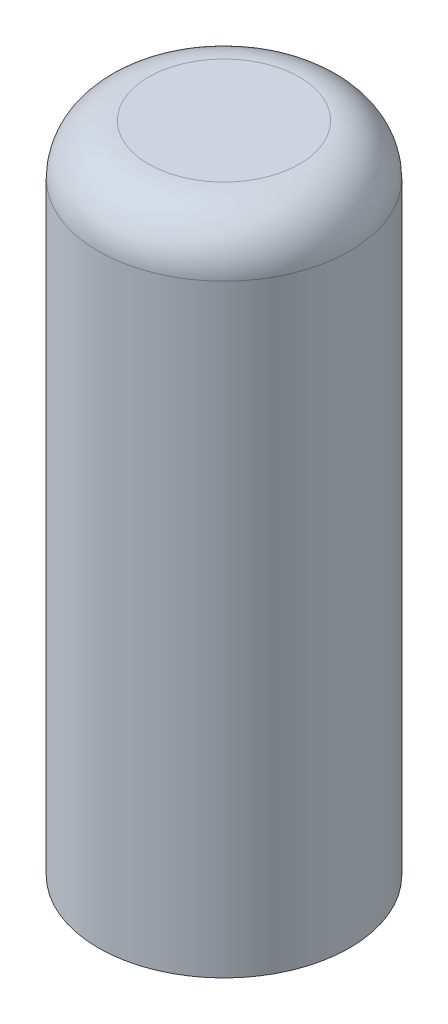
SolidWorks part; units mm, degrees
ref_plane "Front Plane" through (0, 0, 0) normal (0, 0, 1) x (1, 0, 0)
ref_plane "Top Plane" through (0, 0, 0) normal (0, 1, 0) x (1, 0, 0)
ref_plane "Right Plane" through (0, 0, 0) normal (1, 0, 0) x (0, 0, -1)
sketch "Sketch2" plane through (0, 0, 0) normal (0, 1, 0) x (1, 0, 0)
  line L1 (-0.575, 0.6) -> (0.575, 0.6)
  line L2 (-0.575, 0.6) -> (-0.575, -0.6)
  line L3 (-0.575, -0.6) -> (0.575, -0.6)
  line L4 (0.575, 0.6) -> (0.575, -0.6)
  line L5 (-0.575, 0.6) -> (0.575, -0.6) construction
  line L6 (-0.575, -0.6) -> (0.575, 0.6) construction
  circle A0 centre (0, 0) radius 2.5
  dimension "D1" = 5
  dimension "D2" = 1.2
  dimension "D3" = 1.15
extrude "Boss-Extrude1" add sketch "Sketch2" along normal mid plane 13
fillet "Fillet1" radius 1 1 edges at (0, 6.5, 2.5)
sketch "Sketch3" plane through (0, 6.5, 0) normal (0, 1, 0) x (1, 0, 0)
  line L0 (0.575, -0.6) -> (0.575, 0.6) construction
  line L1 (-0.575, -0.6) -> (0.575, -0.6) construction
  line L2 (-0.575, 0.6) -> (-0.575, -0.6) construction
  line L3 (0.575, 0.6) -> (-0.575, 0.6) construction
  line L4 (0.575, -0.6) -> (0.575, 0.6)
  line L5 (-0.575, -0.6) -> (0.575, -0.6)
  line L6 (-0.575, 0.6) -> (-0.575, -0.6)
  line L7 (0.575, 0.6) -> (-0.575, 0.6)
extrude "Boss-Extrude5" add sketch "Sketch3" against normal blind 1
